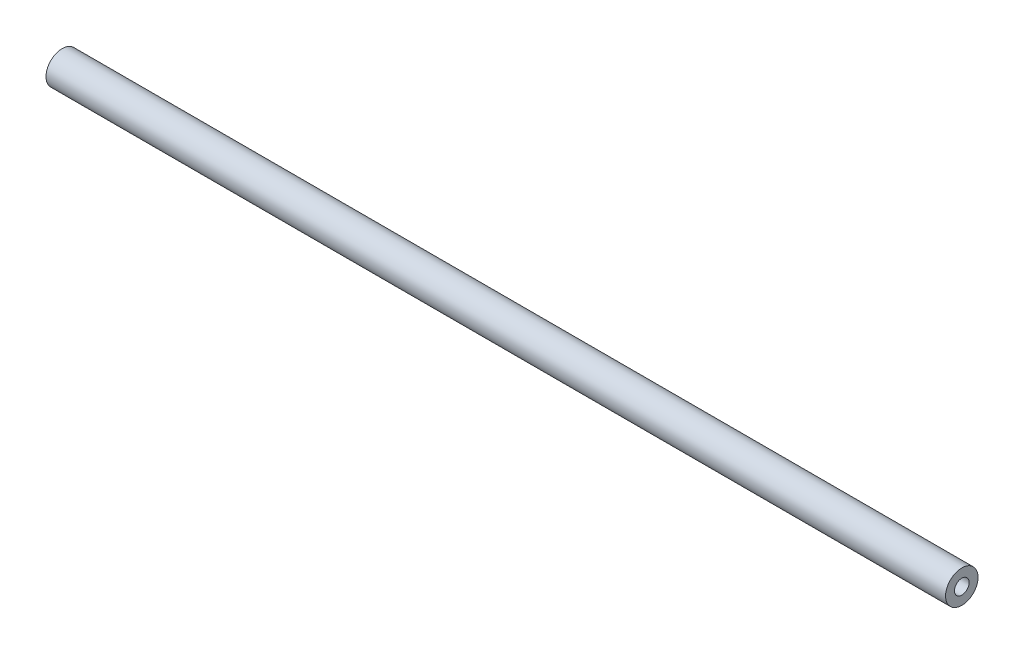
SolidWorks part; units mm, degrees
material "AISI Type A2 Tool Steel"
ref_plane "Front Plane" through (0, 0, 0) normal (0, 0, 1) x (1, 0, 0)
ref_plane "Top Plane" through (0, 0, 0) normal (0, 1, 0) x (1, 0, 0)
ref_plane "Right Plane" through (0, 0, 0) normal (1, 0, 0) x (0, 0, -1)
sketch "Sketch1" plane through (0, 0, 0) normal (0, 0, 1) x (1, 0, 0)
  line L0 (-686.6124, 12.6401) -> (0, 12.6401) construction
  line L1 (0, 12.6401) -> (0, 0) construction
  line L3 (-613.42, 16.9451) -> (-591.2862, 16.9451)
  line L4 (-613.42, 22.1651) -> (-85.58, 22.1651)
  line L5 (-613.42, 22.1651) -> (-613.42, 16.9451)
  line L6 (-588.8008, 12.6401) -> (-110.1992, 12.6401)
  line L7 (-85.58, 22.1651) -> (-85.58, 16.9451)
  line L8 (-591.2862, 16.9451) -> (-588.8008, 12.6401)
  line L9 (-85.58, 16.9451) -> (-107.7138, 16.9451)
  line L10 (-107.7138, 16.9451) -> (-110.1992, 12.6401)
  line L13 (-613.42, 12.6401) -> (-610.1, 12.6401) construction
  line L14 (-613.42, 3.1151) -> (-613.42, 22.1651) construction
  line L15 (-85.58, 22.1651) -> (-85.58, 3.1151) construction
  dimension "D1" = 19.05
  dimension "D2" = 60
  dimension "D3" = 60
revolve "Revolve1" add sketch "Sketch1" angle 360 about L0
